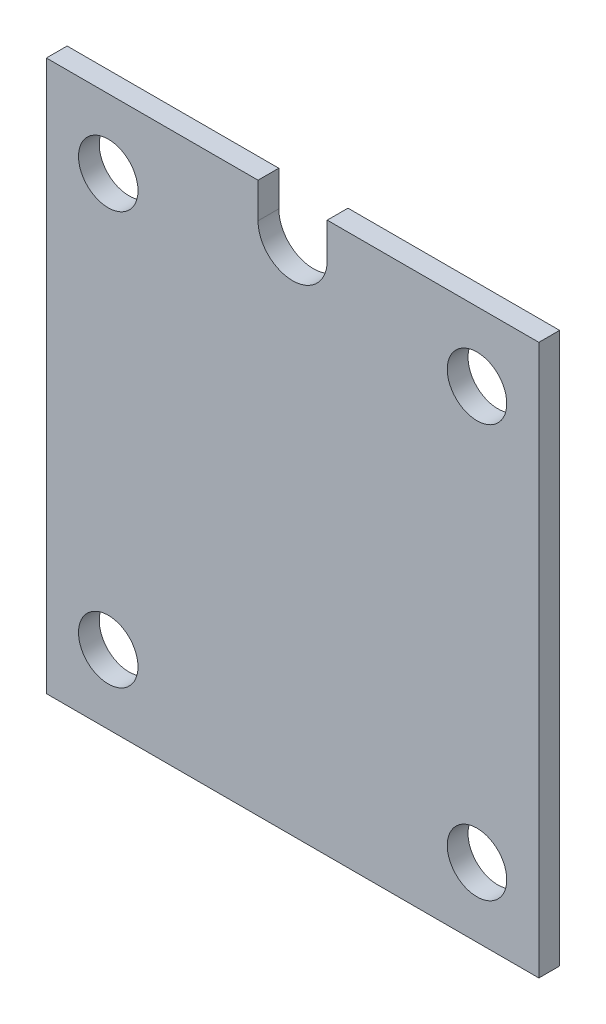
SolidWorks part; units mm, degrees
ref_plane "Front Plane" through (0, 0, 0) normal (0, 0, 1) x (1, 0, 0)
ref_plane "Top Plane" through (0, 0, 0) normal (0, 1, 0) x (1, 0, 0)
ref_plane "Right Plane" through (0, 0, 0) normal (1, 0, 0) x (0, 0, -1)
sketch "Sketch1" plane through (0, 0, 0) normal (0, 0, 1) x (1, 0, 0)
  line L0 (0, 34.7) -> (0, 58.7557) construction
  line L1 (-35.5928, -39.7849) -> (35.5928, -39.7849)
  line L2 (-35.5928, -39.7849) -> (-35.5928, 39.7849)
  line L3 (-35.5928, 39.7849) -> (35.5928, 39.7849)
  line L4 (35.5928, -39.7849) -> (35.5928, 39.7849)
  line L5 (-35.5928, -39.7849) -> (35.5928, 39.7849) construction
  line L6 (-35.5928, 39.7849) -> (35.5928, -39.7849) construction
  line L7 (-26.65, -29.8) -> (26.65, -29.8) construction
  line L8 (-26.65, -29.8) -> (-26.65, 29.8) construction
  line L9 (-26.65, 29.8) -> (26.65, 29.8) construction
  line L10 (26.65, -29.8) -> (26.65, 29.8) construction
  line L11 (-26.65, -29.8) -> (26.65, 29.8) construction
  line L12 (-26.65, 29.8) -> (26.65, -29.8) construction
  line L13 (-5, 34.7) -> (-5, 58.7557)
  line L14 (5, 34.7) -> (5, 58.7557)
  circle A0 centre (26.65, 29.8) radius 4.3
  circle A1 centre (26.65, -29.8) radius 4.3
  circle A2 centre (-26.65, -29.8) radius 4.3
  circle A3 centre (-26.65, 29.8) radius 4.3
  arc A5 (-5, 34.7) -> (5, 34.7) centre (0, 34.7) ccw
  arc A6 (5, 58.7557) -> (-5, 58.7557) centre (0, 58.7557) ccw
  point P0 (0, 0)
  point P6 (0, 0)
  point P15 (0, 46.7278)
  point P23 (0, 27.8518)
  point P24 (0, 38.2856)
  point P25 (0, 58.7557)
  point P26 (-35.5928, 39.7849)
  dimension "D1" = 8.6
  dimension "D4" = 4.9
  dimension "D5" = 10
  dimension "D2" = 59.6
  dimension "D3" = 53.3
extrude "Boss-Extrude1" add sketch "Sketch1" along normal blind 3 contours A5 L13 L3 L2 L1 L4 L14 A3 A2 A1 A0 region at (0, -0.594, 0)
